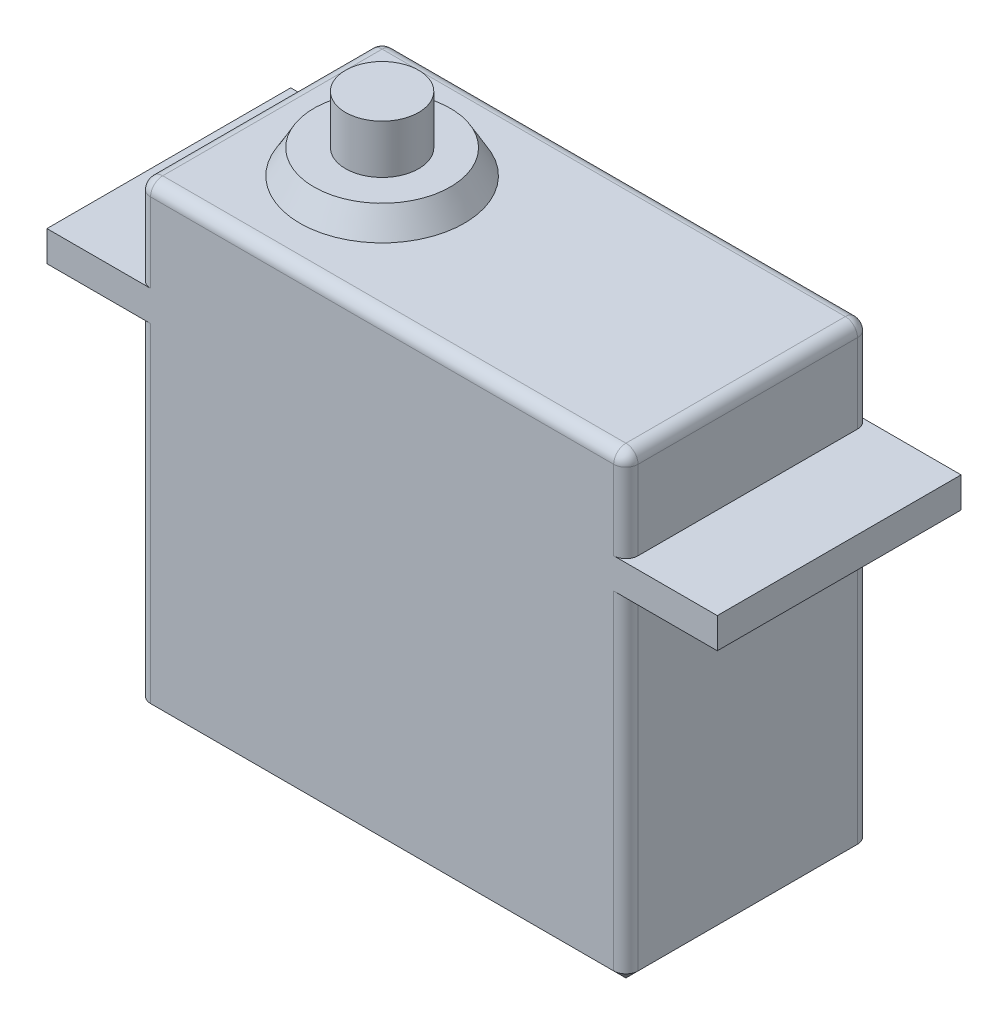
SolidWorks part; units mm, degrees
material "ABS"
ref_plane "Front Plane" through (0, 0, 0) normal (0, 0, 1) x (1, 0, 0)
ref_plane "Top Plane" through (0, 0, 0) normal (0, 1, 0) x (1, 0, 0)
ref_plane "Right Plane" through (0, 0, 0) normal (1, 0, 0) x (0, 0, -1)
sketch "Sketch1" plane through (0, 0, 0) normal (0, 1, 0) x (1, 0, 0)
  line L1 (0, 0) -> (40, 0)
  line L2 (0, 0) -> (0, 20)
  line L3 (0, 20) -> (40, 20)
  line L4 (40, 0) -> (40, 20)
  dimension "D1" = 40
  dimension "D2" = 20
extrude "Boss-Extrude1" add sketch "Sketch1" along normal blind 28
sketch "Sketch2" plane through (0, 28, 0) normal (0, 1, 0) x (1, 0, 0)
  line L0 (0, 0) -> (40, 0) construction
  line L1 (47.5, 20) -> (-7.5, 20)
  line L2 (47.5, 20) -> (47.5, 0)
  line L3 (47.5, 0) -> (-7.5, 0)
  line L4 (-7.5, 20) -> (-7.5, 0)
  line L8 (20, 20) -> (20, 0) construction
  line L9 (0, 20) -> (40, 20) construction
  dimension "D1" = 55
extrude "Boss-Extrude2" add sketch "Sketch2" along normal blind 2.5
sketch "Sketch3" plane through (0, 30.5, 0) normal (0, 1, 0) x (1, 0, 0)
  line L0 (47.5, 20) -> (-7.5, 20) construction
  line L1 (0, 20) -> (40, 20)
  line L2 (0, 20) -> (0, 0)
  line L3 (0, 0) -> (40, 0)
  line L4 (40, 20) -> (40, 0)
  line L5 (-7.5, 0) -> (47.5, 0) construction
  line L6 (40, 0) -> (40, 20) construction
  line L7 (0, 20) -> (0, 0) construction
extrude "Boss-Extrude3" add sketch "Sketch3" along normal blind 7.5
sketch "Sketch4" plane through (0, 38, 0) normal (0, 1, 0) x (1, 0, 0)
  line L0 (0, 10) -> (10, 10) construction
  line L1 (0, 20) -> (0, 0) construction
  circle A0 centre (10, 10) radius 6.75
  dimension "D1" = 13.5
  dimension "D2" = 10
extrude "Boss-Extrude4" add sketch "Sketch4" along normal blind 2
sketch "Sketch5" plane through (0, 40, 0) normal (0, 1, 0) x (1, 0, 0)
  circle A0 centre (10, 10) radius 3
  dimension "D1" = 6
extrude "Boss-Extrude5" add sketch "Sketch5" along normal blind 4
fillet "Fillet1" radius 1 12 edges at (20, 38, -20) (40, 38, -10) (0, 38, -10) (20, 38, 0)
chamfer "Chamfer1" distance 1 angle 45 8 edges at (20, 0, 0) (0, 0, -10) (40, 0, -10) (39.7071, 0, -0.2929) (0.2929, 0, -0.2929) (39.7071, 0, -19.7071) (0.2929, 0, -19.7071) (20, 0, -20)
chamfer "Chamfer2" distance 2 angle 30 1 edges at (10, 40, -3.25) first distance on face at (10, 40, -3.25)
ref_plane "Plane1" through (10, 0, 0) normal (1, 0, 0) x (0, 0, -1)
ref_plane "Plane2" through (0, 0, -10) normal (0, 0, 1) x (1, 0, 0)
ref_axis "Axis1" through (10, 46.2, -10) along (0, -1, 0)
